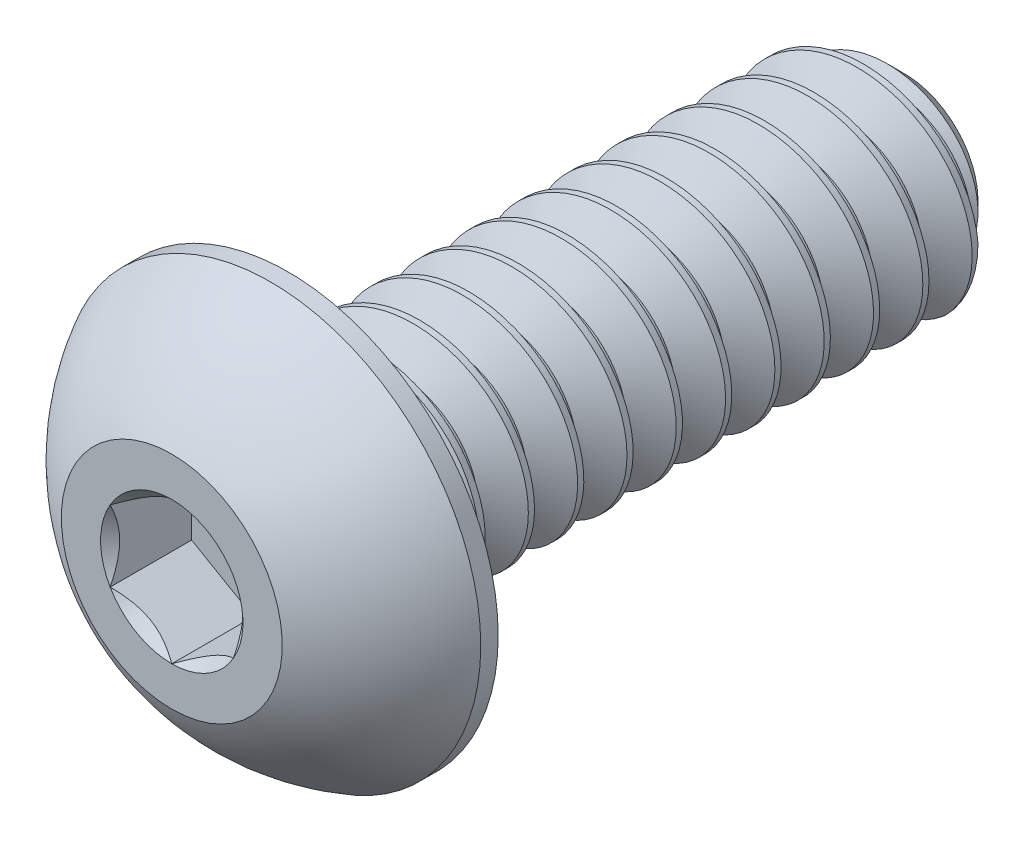
SolidWorks part; units mm, degrees
ref_plane "Front" through (0, 0, 0) normal (0, 0, 1) x (1, 0, 0)
ref_plane "Top" through (0, 0, 0) normal (0, 1, 0) x (1, 0, 0)
ref_plane "Right" through (0, 0, 0) normal (1, 0, 0) x (0, 0, -1)
sketch "Sketch1" plane through (0, 0, 0) normal (1, 0, 0) x (0, 0, -1)
  line L2 (1.4986, 1.4224) -> (9.4361, 1.4224) construction
  line L3 (9.4361, 1.4224) -> (9.4361, 0) construction
  line L4 (9.4361, 0) -> (1.4986, 0) construction
  line L6 (1.2738, 2.7051) -> (1.4986, 2.7051) construction
  line L7 (9.4361, 1.4224) -> (9.4361, -1.4224) construction
  line L8 (0, 0) -> (1.4986, 0) construction
  line L9 (1.4986, 2.7051) -> (1.4986, -2.7051) construction
  line L11 (1.4986, 1.4224) -> (1.4986, 0) construction
  line L13 (0, 0.7938) -> (0, -0.7938) construction
  line L14 (0, 0.7938) -> (0, 1.4224) construction
  arc A3 (0, 1.4224) -> (1.2738, 2.7051) centre (2.7151, 0) cw construction
  point P10 (7.8486, -1.4224)
  dimension "D1" = 0.2248
  dimension "D2" = 1.5875
sketch "Sketch11" plane through (0, 0, 0) normal (1, 0, 0) x (0, 0, -1)
  line L1 (1.4986, 0) -> (9.4361, 0)
  line L4 (1.4986, 1.4224) -> (9.4361, 1.4224) construction
  line L5 (9.4361, 1.4224) -> (9.4361, 0) construction
  line L8 (1.4986, 1.4224) -> (9.4361, 1.4224)
  line L9 (9.4361, 1.4224) -> (9.4361, 0)
  line L10 (1.4986, 1.4224) -> (1.4986, 0)
revolve "Revolve1" add sketch "Sketch11" angle 360 about L1
chamfer "Chamfer1" distance 0.4763 angle 45 1 edges at (0, -1.4224, -9.4361)
sketch "Sketch7" plane through (0, 0, 0) normal (1, 0, 0) x (0, 0, -1)
  line L6 (1.2738, 2.7051) -> (1.4986, 2.7051) construction
  line L8 (0, 0) -> (1.4986, 0) construction
  line L11 (1.4986, 2.7051) -> (1.4986, -2.7051) construction
  line L12 (1.2738, 2.7051) -> (1.4986, 2.7051)
  line L13 (0, 0) -> (1.4986, 0)
  line L14 (0, 0.7938) -> (0, -0.7938) construction
  line L15 (1.4986, 2.7051) -> (1.4986, 0)
  line L16 (0, 1.4224) -> (0, 0)
  arc A2 (1.2738, 2.7051) -> (0, 1.4224) centre (2.7151, 0) ccw construction
  arc A3 (1.2738, 2.7051) -> (0, 1.4224) centre (2.7151, 0) ccw
revolve "Revolve2" add sketch "Sketch7" angle 360 mid plane about L13
sketch "Sketch5" plane through (0, 0, 0) normal (0, 0, 1) x (1, 0, 0)
  line L1 (0.7938, -0.4583) -> (0.7938, 0.4583)
  line L2 (0.7938, 0.4583) -> (0, 0.9165)
  line L3 (0, 0.9165) -> (-0.7937, 0.4583)
  line L4 (-0.7937, 0.4583) -> (-0.7937, -0.4583)
  line L5 (-0.7937, -0.4583) -> (0, -0.9165)
  line L6 (0, -0.9165) -> (0.7938, -0.4583)
  circle A0 centre (0, 0) radius 0.7938 construction
extrude "Cut-Extrude2" cut sketch "Sketch5" against normal blind 1.049
sketch "Sketch6" plane through (0, 0, 0) normal (0, 0, 1) x (1, 0, 0)
  circle A0 centre (0, 0) radius 0.9165
extrude "Cut-Extrude3" cut sketch "Sketch6" against normal blind 1.049 draft 45
sketch "Sketch3" plane through (0, 0, -9.4361) normal (0, 0, -1) x (-1, 0, 0)
  circle A0 centre (0, 0) radius 1.4224
curve "Helix/Spiral1" pitch 0.635 height 8.5725 radius 1.4224 centre (0, 0, -9.4361) axis (0, 0, 1) start towards (0, 1, 0)
sketch "Sketch2" plane through (0, 0, 0) normal (1, 0, 0) x (0, 0, -1)
  line L0 (9.4361, 1.4224) -> (9.9917, 1.4224)
  line L1 (9.9917, 1.4224) -> (9.7536, 1.01)
  line L2 (9.7536, 1.01) -> (9.6742, 1.01)
  line L3 (9.6742, 1.01) -> (9.4361, 1.4224)
  line L4 (9.5552, 1.2162) -> (9.8727, 1.2162) construction
  dimension "D1" = 60
  dimension "D2" = 0.0794
  dimension "D3" = 0.3175
sweep "Cut-Sweep1" cut profiles "Sketch2" path "Helix/Spiral1"
sketch "Sketch9" [suppressed] plane through (0, 0, -6.731) normal (0, 0, 1) x (1, 0, 0)
  circle A2 centre (0, 0) radius 6.35
extrude "Boss-Extrude2" [suppressed] add sketch "Sketch9" against normal offset from surface (69.85 mm away) 31.75 up to face at (0, -0.9462, -9.4361)
ref_axis "Center Axis 1" through (0, 0, -8.9599) along (0, 0, 1)
ref_plane "Contact Plane 1" through (0, 0, -1.4986) normal (0, 0, -1) x (-1, 0, 0)
ref_plane "Contact Plane 2" through (0, 0, -9.4361) normal (0, 0, -1) x (-1, 0, 0)
equation "\"D3@Helix/Spiral1\" = \"Lg@Sketch1\" + \"D4@Helix/Spiral1\""
equation "\"D2@Sketch2\" = \"D4@Helix/Spiral1\" * .125"
equation "\"D3@Sketch2\" = \"D4@Helix/Spiral1\" * .5"
equation "\"D1@Chamfer1\" = \"D4@Helix/Spiral1\" * .75"
equation "\"D1@Cut-Extrude2\" = \"Head Ht@Sketch1\" * .7"
equation "\"D1@Sketch1\" = \"Head Ht@Sketch1\" * .15"
equation "\"D1@Cut-Extrude3\" = \"D1@Cut-Extrude2\""
equation "\"D1@Chamfer1\"=\"D4@Helix/Spiral1\" * .75"
equation "\"D2@Sketch1\"=\"D4@Helix/Spiral1\"*2.5"
